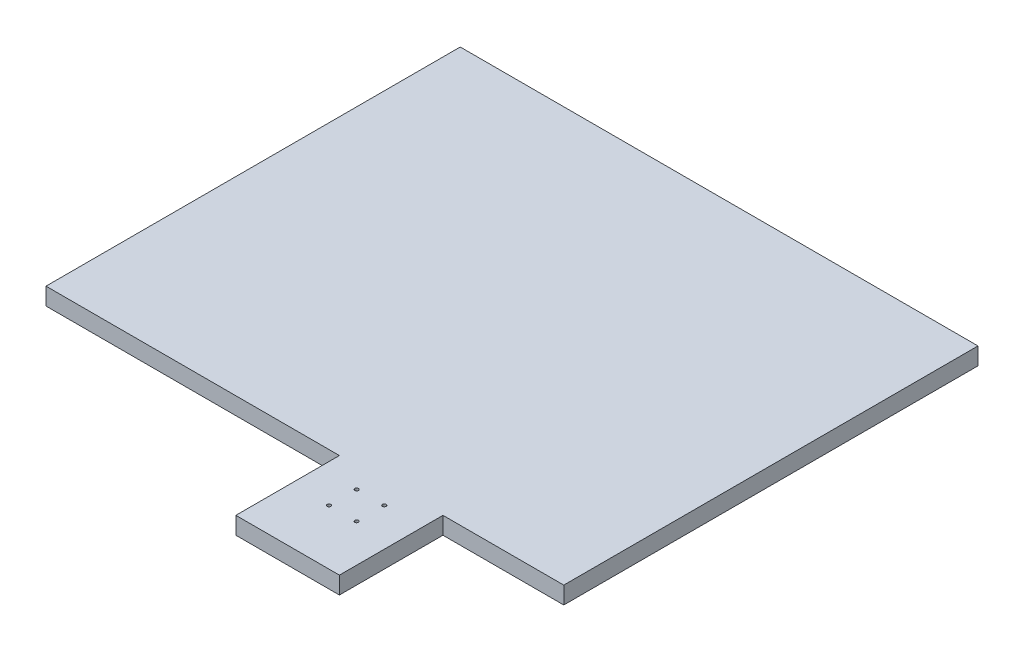
SolidWorks part; units mm, degrees
ref_plane "前基準面" through (0, 0, 0) normal (0, 0, 1) x (1, 0, 0)
ref_plane "上基準面" through (0, 0, 0) normal (0, 1, 0) x (1, 0, 0)
ref_plane "右基準面" through (0, 0, 0) normal (1, 0, 0) x (0, 0, -1)
sketch "草圖1" plane through (0, 0, 0) normal (0, 1, 0) x (1, 0, 0)
  line L0 (50, -1010.2) -> (50, 48989.8) construction
  line L1 (-150, -120) -> (20, -120)
  line L2 (-150, -120) -> (-150, 120)
  line L3 (-150, 120) -> (150, 120)
  line L4 (150, -120) -> (150, 120)
  line L5 (-150, -120) -> (150, 120) construction
  line L6 (-150, 120) -> (150, -120) construction
  line L7 (20, -120) -> (20, -180)
  line L8 (20, -180) -> (80, -180)
  line L9 (80, -180) -> (80, -120)
  line L10 (80, -120) -> (150, -120)
  point P0 (0, 0)
  point P10 (50, -180)
  dimension "D1" = 300
  dimension "D2" = 240
  dimension "D3" = 200
  dimension "D4" = 60
  dimension "D5" = 60
extrude "填料-伸長1" add sketch "草圖1" along normal blind 10
sketch "草圖2" plane through (0, 0, 0) normal (0, -1, 0) x (1, 0, 0)
  line L0 (-980, 140) -> (49020, 140) construction
  line L2 (50, -820) -> (50, 49180) construction
  line L3 (20, 180) -> (80, 180) construction
  line L4 (-150, 120) -> (20, 120) construction
  line L6 (60, 150) -> (40, 150)
  line L7 (60, 150) -> (60, 130)
  line L8 (60, 130) -> (40, 130)
  line L9 (40, 150) -> (40, 130)
  line L10 (60, 150) -> (40, 130) construction
  line L11 (60, 130) -> (40, 150) construction
  circle A0 centre (42, 132) radius 1.05
  circle A1 centre (42, 148) radius 1.05
  circle A2 centre (58, 132) radius 1.05
  circle A3 centre (58, 148) radius 1.05
  point P7 (50, 180)
  point P17 (50, 140)
  point P22 (0, 0)
  dimension "D4" = 2.1
  dimension "D1" = 20
  dimension "D2" = 8
  dimension "D3" = 8
  dimension "D5" = 20
  dimension "D6" = 20
extrude "除料-伸長1" cut sketch "草圖2" against normal blind 8 contours L6 L9 L8 L7 A3 A1 A0 A2 region at (50, 0, 140)
extrude "除料-伸長2" cut sketch "草圖2<3>" against normal through all contours A2 | A0 | A1 | A3
sketch "草圖2<3>" plane through (0, 0, 0) normal (0, -1, 0) x (1, 0, 0) same geometry as "草圖2"
